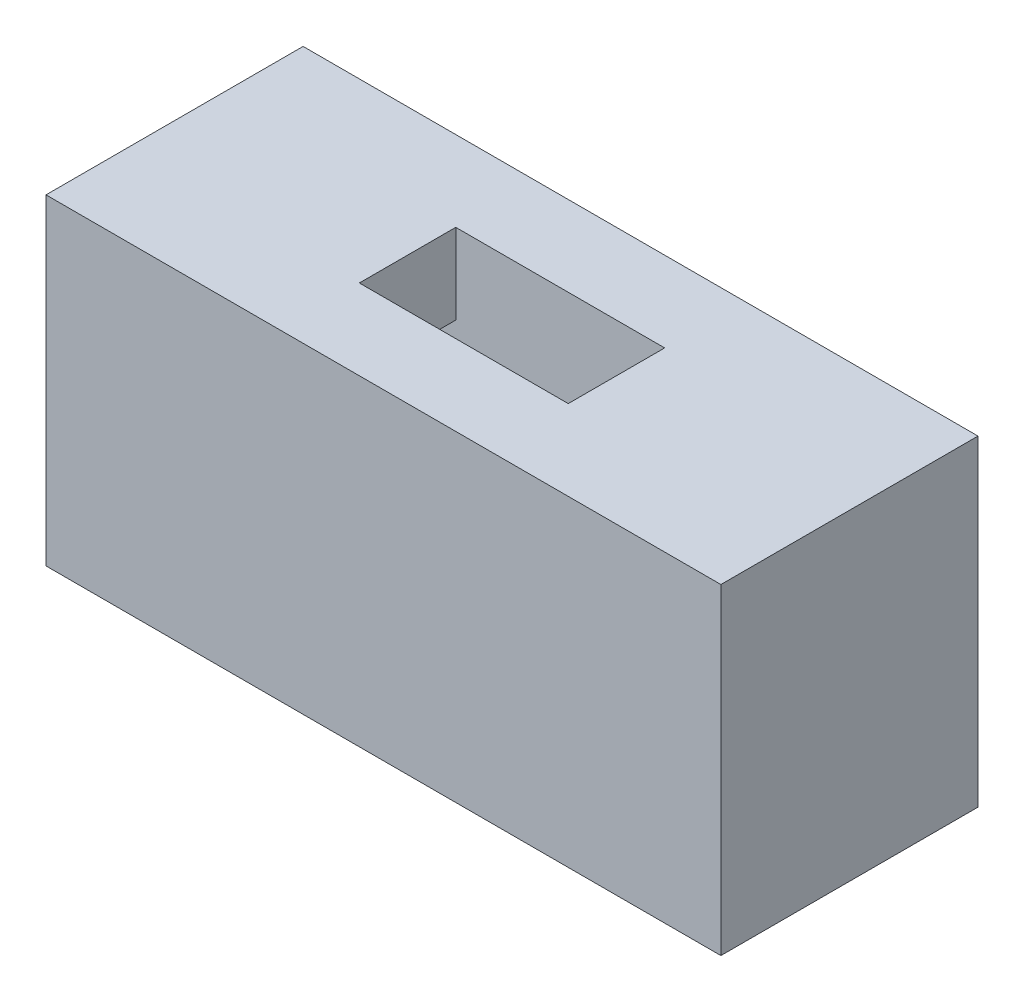
SolidWorks part; units mm, degrees
ref_plane "Plan de face" through (0, 0, 0) normal (0, 0, 1) x (1, 0, 0)
ref_plane "Plan de dessus" through (0, 0, 0) normal (0, 1, 0) x (1, 0, 0)
ref_plane "Plan de droite" through (0, 0, 0) normal (1, 0, 0) x (0, 0, -1)
sketch "Esquisse1" plane through (0, 0, 0) normal (0, 1, 0) x (1, 0, 0)
  line L1 (-21, 8) -> (21, 8)
  line L2 (-21, 8) -> (-21, -8)
  line L3 (-21, -8) -> (21, -8)
  line L4 (21, 8) -> (21, -8)
  line L5 (-21, 8) -> (21, -8) construction
  line L6 (-21, -8) -> (21, 8) construction
  point P0 (0, 0)
  dimension "D1" = 42
  dimension "D2" = 16
extrude "Boss.-Extru.1" add sketch "Esquisse1" along normal blind 20
sketch "Esquisse2" plane through (0, 20, 0) normal (0, 1, 0) x (1, 0, 0)
  line L1 (-6.5, -3) -> (6.5, -3)
  line L2 (-6.5, -3) -> (-6.5, 3)
  line L3 (-6.5, 3) -> (6.5, 3)
  line L4 (6.5, -3) -> (6.5, 3)
  line L5 (-6.5, -3) -> (6.5, 3) construction
  line L6 (-6.5, 3) -> (6.5, -3) construction
  point P0 (0, 0)
  dimension "D1" = 13
  dimension "D2" = 6
extrude "Enlèv. mat.-Extru.1" cut sketch "Esquisse2" against normal blind 10
sketch "Esquisse3" plane through (-6.5, 0, 0) normal (1, 0, 0) x (0, 0, -1)
  line L0 (3, 10) -> (3, 20) construction
  line L1 (-3, 10) -> (3, 10)
  line L2 (-3, 10) -> (-3, 15)
  line L3 (-3, 15) -> (3, 15)
  line L4 (3, 10) -> (3, 15)
extrude "Enlèv. mat.-Extru.2" cut sketch "Esquisse3" against normal through all
